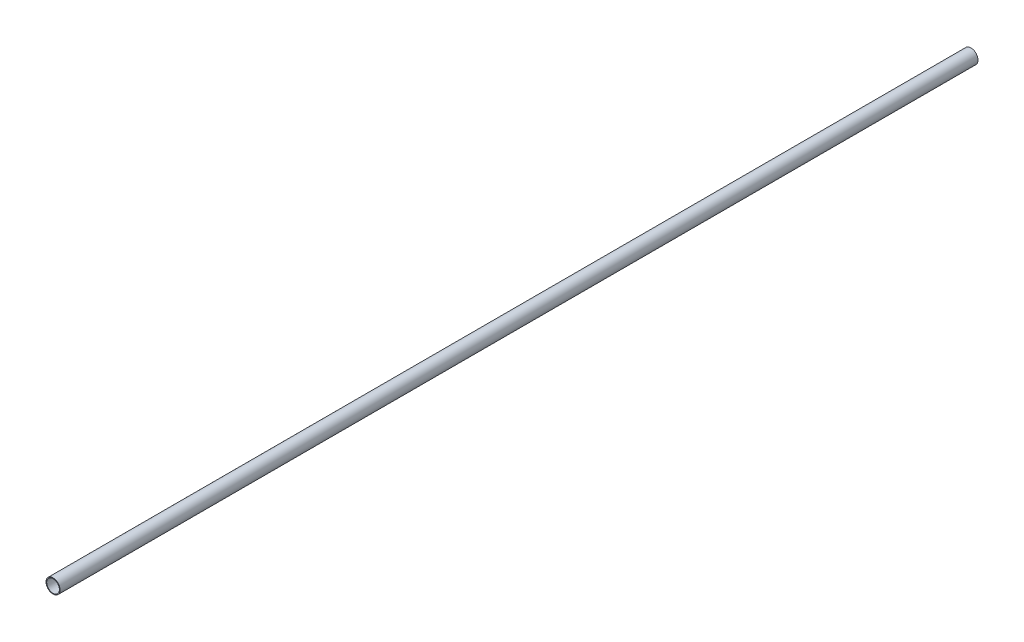
SolidWorks part; units mm, degrees
material "carbon fiber"
ref_plane "Front Plane" through (0, 0, 0) normal (0, 0, 1) x (1, 0, 0)
ref_plane "Top Plane" through (0, 0, 0) normal (0, 1, 0) x (1, 0, 0)
ref_plane "Right Plane" through (0, 0, 0) normal (1, 0, 0) x (0, 0, -1)
sketch "Эскиз1" plane through (0, 0, 0) normal (0, 0, 1) x (1, 0, 0)
  circle A0 centre (0, 0) radius 10
  circle A1 centre (0, 0) radius 9
  dimension "D1" = 20
  dimension "D2" = 1
extrude "Бобышка-Вытянуть1" add sketch "Эскиз1" along normal mid plane 1300
